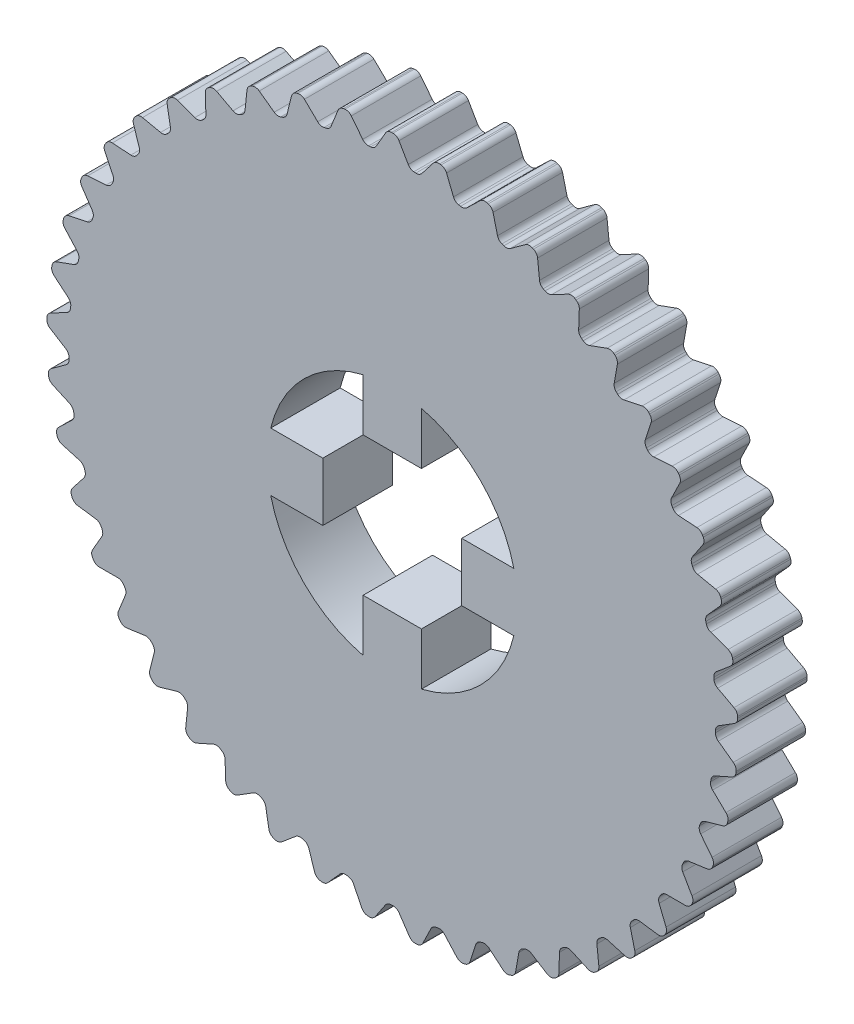
SolidWorks part; units mm, degrees
ref_plane "Front Plane" through (0, 0, 0) normal (0, 0, 1) x (1, 0, 0)
ref_plane "Top Plane" through (0, 0, 0) normal (0, 1, 0) x (1, 0, 0)
ref_plane "Right Plane" through (0, 0, 0) normal (1, 0, 0) x (0, 0, -1)
sketch "Sketch1" plane through (0, 0, 0) normal (0, 0, 1) x (1, 0, 0)
  line L0 (0, 0) -> (0, 15.8015) construction
  line L1 (0, 0) -> (-1.7718, 25.3385) construction
  line L2 (0.2159, 15.8015) -> (-0.2159, 15.8015)
  line L3 (-0.2159, 15.8015) -> (-0.8155, 14.763)
  line L4 (0.2159, 15.8015) -> (0.8155, 14.763)
  circle A0 centre (0, 0) radius 14.7855 construction
  arc A1 (-0.8155, 14.763) -> (-1.0314, 14.7494) centre (0, 0) ccw
  arc A2 (-1.0314, 14.7494) -> (1.0314, 14.7494) centre (0, 14.7855) ccw
  arc A3 (0.8155, 14.763) -> (1.0314, 14.7494) centre (0, 0) cw
  point P3 (0, 14.7855)
  dimension "D1" = 4
  dimension "D5" = 0.2159
  dimension "D2" = 1.016
  dimension "D3" = 0.2159
  dimension "D4" = 30
extrude "Boss-Extrude1" add sketch "Sketch1" along normal blind 3.175
sketch "Sketch6" plane through (0, 0, 0) normal (0, 0, 1) x (1, 0, 0)
  circle A0 centre (0, 0) radius 14.7855
  arc A1 (-0.8155, 14.763) -> (-1.0314, 14.7494) centre (0, 0) ccw construction
extrude "Boss-Extrude2" add sketch "Sketch6" along normal blind 3.175
fillet "Fillet1" radius 0.3175 4 edges at (-0.8155, 14.763, 1.5875) (0.8155, 14.763, 1.5875) (0.2159, 15.8015, 1.5875) (-0.2159, 15.8015, 1.5875)
pattern_circular "CirPattern3" count 45 over 360 about axis through (0, 0, 3.175) along (0, 0, 1) of "Boss-Extrude1", "Fillet1"
sketch "Sketch7" plane through (0, 0, 3.175) normal (0, 0, 1) x (1, 0, 0)
  line L1 (-1.3335, 6.096) -> (1.3335, 6.096)
  line L2 (-1.3335, 6.096) -> (-1.3335, -6.096)
  line L3 (-1.3335, -6.096) -> (1.3335, -6.096)
  line L4 (1.3335, 6.096) -> (1.3335, -6.096)
  line L5 (-6.096, 1.3335) -> (6.096, 1.3335)
  line L6 (-6.096, 1.3335) -> (-6.096, -1.3335)
  line L7 (-6.096, -1.3335) -> (6.096, -1.3335)
  line L8 (6.096, 1.3335) -> (6.096, -1.3335)
  line L9 (-3.175, 1.3335) -> (3.175, 1.3335)
  line L10 (-3.175, 1.3335) -> (-3.175, -1.3335)
  line L11 (-3.175, -1.3335) -> (3.175, -1.3335)
  line L12 (3.175, 1.3335) -> (3.175, -1.3335)
  line L13 (-1.3335, 3.175) -> (1.3335, 3.175)
  line L14 (-1.3335, 3.175) -> (-1.3335, -3.175)
  line L15 (-1.3335, -3.175) -> (1.3335, -3.175)
  line L16 (1.3335, 3.175) -> (1.3335, -3.175)
  circle A0 centre (0, 0) radius 5.715
  point P7 (0, 6.096)
  point P8 (1.3335, 0)
  point P13 (0, 1.3335)
  point P14 (6.096, 0)
  dimension "D1" = 11.43
  dimension "D2" = 2.667
  dimension "D3" = 12.192
  dimension "D4" = 2.667
  dimension "D5" = 12.192
  dimension "D6" = 6.35
  dimension "D7" = 3.175
  dimension "D8" = 3.175
  dimension "D9" = 6.35
extrude "Cut-Extrude1" cut sketch "Sketch7" against normal blind 3.175 contours L5 A0 L4 | L2 A0 L5 | L2 L7 L4 L5 | L4 A0 L7 | L7 A0 L2 | L2 L15 L4 L7 | L5 L10 L7 L2 | L13 L2 L5 L4 | L12 L5 L4 L7 region at (-3.0023, 3.0023, 3.175) region at (3.0023, 3.0023, 3.175) region at (0, 2.2542, 3.175) region at (0, 0, 3.175) region at (-2.2542, 0, 3.175) region at (-3.0023, -3.0023, 3.175) region at (2.2542, 0, 3.175) region at (0, -2.2543, 3.175) region at (3.0023, -3.0023, 3.175)
equation "\"D4@Sketch7\"=\"D2@Sketch7\""
equation "\"D5@Sketch7\"=\"D3@Sketch7\""
